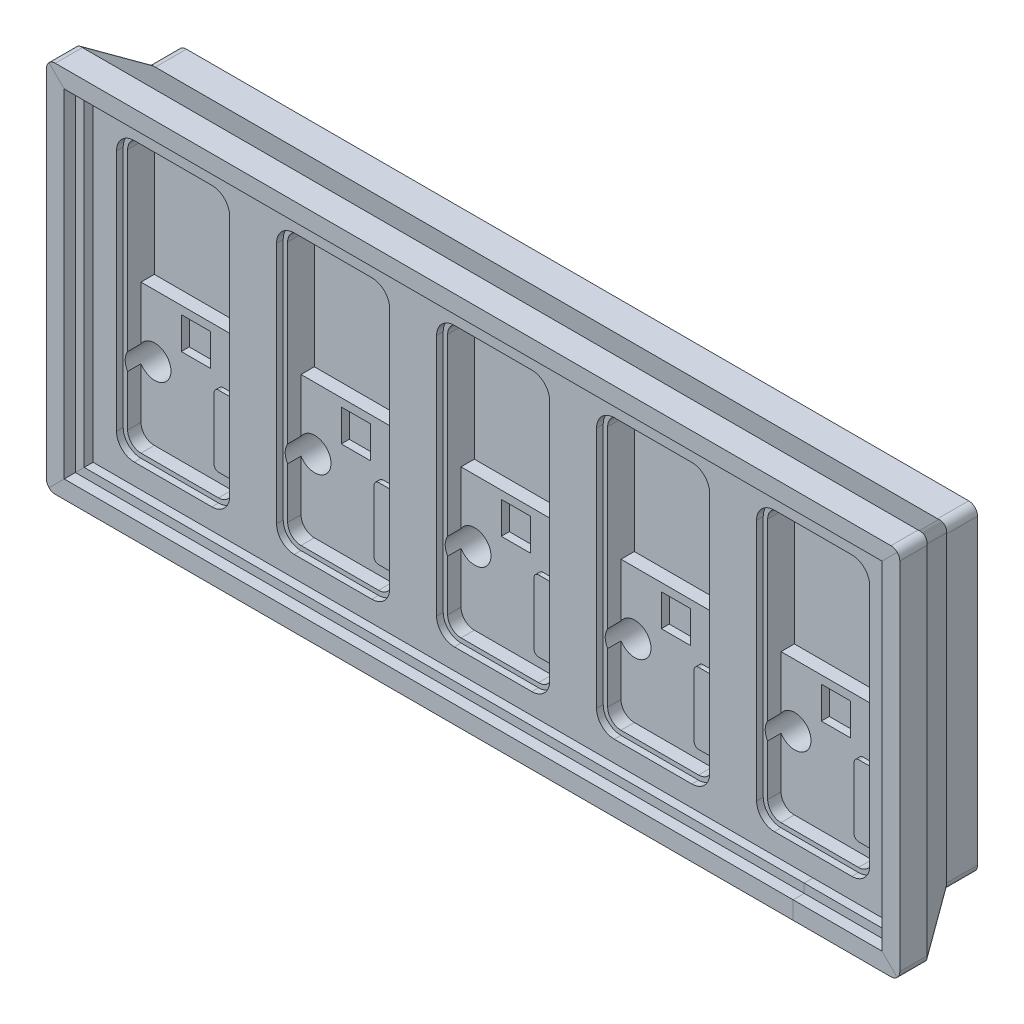
SolidWorks part; units mm, degrees
ref_plane "Ebene vorne" through (0, 0, 0) normal (0, 0, 1) x (1, 0, 0)
ref_plane "Ebene oben" through (0, 0, 0) normal (0, 1, 0) x (1, 0, 0)
ref_plane "Ebene rechts" through (0, 0, 0) normal (1, 0, 0) x (0, 0, -1)
sketch "Skizze1" plane through (0, 0, 0) normal (0, 0, 1) x (1, 0, 0)
  line L1 (-18, -36) -> (18, -36)
  line L2 (-18, -36) -> (-18, 36)
  line L3 (-18, 36) -> (18, 36)
  line L4 (18, -36) -> (18, 36)
  line L5 (-18, -36) -> (18, 36) construction
  line L6 (-18, 36) -> (18, -36) construction
  point P0 (0, 0)
  dimension "D1" = 72
  dimension "D2" = 36
extrude "Aufsatz-Linear austragen1" add sketch "Skizze1" along normal blind 19
sketch "Skizze2" plane through (0, 0, 19) normal (0, 0, 1) x (1, 0, 0)
  line L1 (-8.725, -31.325) -> (8.725, -31.325)
  line L2 (-12.725, -27.325) -> (-12.725, 27.325)
  line L3 (-8.725, 31.325) -> (8.725, 31.325)
  line L4 (12.725, -27.325) -> (12.725, 27.325)
  line L5 (-12.725, -31.325) -> (12.725, 31.325) construction
  line L6 (-12.725, 31.325) -> (12.725, -31.325) construction
  arc A0 (-12.725, -27.325) -> (-8.725, -31.325) centre (-8.725, -27.325) ccw
  arc A1 (8.725, -31.325) -> (12.725, -27.325) centre (8.725, -27.325) ccw
  arc A2 (8.725, 31.325) -> (12.725, 27.325) centre (8.725, 27.325) cw
  arc A3 (-12.725, 27.325) -> (-8.725, 31.325) centre (-8.725, 27.325) cw
  point P0 (0, 0)
  dimension "4" = 4
  dimension "D2" = 25.45
  dimension "D3" = 62.65
extrude "Schnitt-Linear austragen1" cut sketch "Skizze2" against normal blind 1.5
sketch "Skizze3" plane through (0, 0, 17.5) normal (0, 0, 1) x (1, 0, 0)
  line L8 (-8.725, -30.325) -> (8.725, -30.325)
  line L9 (11.725, -27.325) -> (11.725, 27.325)
  line L10 (8.725, 30.325) -> (-8.725, 30.325)
  line L11 (-11.725, 27.325) -> (-11.725, -27.325)
  line L12 (-8.725, -30.325) -> (8.725, -30.325)
  line L13 (11.725, -27.325) -> (11.725, 27.325)
  line L14 (8.725, 30.325) -> (-8.725, 30.325)
  line L15 (-11.725, 27.325) -> (-11.725, -27.325)
  arc A8 (-11.725, -27.325) -> (-8.725, -30.325) centre (-8.725, -27.325) ccw
  arc A9 (8.725, -30.325) -> (11.725, -27.325) centre (8.725, -27.325) ccw
  arc A10 (11.725, 27.325) -> (8.725, 30.325) centre (8.725, 27.325) ccw
  arc A11 (-8.725, 30.325) -> (-11.725, 27.325) centre (-8.725, 27.325) ccw
  arc A12 (-11.725, -27.325) -> (-8.725, -30.325) centre (-8.725, -27.325) ccw
  arc A13 (8.725, -30.325) -> (11.725, -27.325) centre (8.725, -27.325) ccw
  arc A14 (11.725, 27.325) -> (8.725, 30.325) centre (8.725, 27.325) ccw
  arc A15 (-8.725, 30.325) -> (-11.725, 27.325) centre (-8.725, 27.325) ccw
  dimension "D1" = 1
extrude "Schnitt-Linear austragen2" cut sketch "Skizze3" against normal blind 3
sketch "Skizze4" plane through (0, 0, 14.5) normal (0, 0, 1) x (1, 0, 0)
  line L0 (-11.725, 0) -> (11.725, 0)
  line L1 (-11.725, 0) -> (-11.725, 27.325)
  line L2 (11.725, 27.325) -> (11.725, 0)
  line L4 (-8.725, -30.325) -> (8.725, -30.325)
  line L5 (11.725, -27.325) -> (11.725, 27.325)
  line L6 (8.725, 30.325) -> (-8.725, 30.325)
  line L7 (-11.725, 27.325) -> (-11.725, -27.325)
  line L8 (-8.725, -30.325) -> (8.725, -30.325) construction
  line L9 (11.725, -27.325) -> (11.725, 27.325) construction
  line L10 (8.725, 30.325) -> (-8.725, 30.325)
  line L11 (-11.725, 27.325) -> (-11.725, -27.325) construction
  arc A4 (-11.725, -27.325) -> (-8.725, -30.325) centre (-8.725, -27.325) ccw
  arc A5 (8.725, -30.325) -> (11.725, -27.325) centre (8.725, -27.325) ccw
  arc A6 (11.725, 27.325) -> (8.725, 30.325) centre (8.725, 27.325) ccw
  arc A7 (-8.725, 30.325) -> (-11.725, 27.325) centre (-8.725, 27.325) ccw
  arc A8 (-11.725, -27.325) -> (-8.725, -30.325) centre (-8.725, -27.325) ccw construction
  arc A9 (8.725, -30.325) -> (11.725, -27.325) centre (8.725, -27.325) ccw construction
  arc A10 (11.725, 27.325) -> (8.725, 30.325) centre (8.725, 27.325) ccw
  arc A11 (-8.725, 30.325) -> (-11.725, 27.325) centre (-8.725, 27.325) ccw
  dimension "D1" = 0
extrude "Schnitt-Linear austragen3" cut sketch "Skizze4" against normal blind 3
sketch "Skizze5" plane through (0, 0, 17.5) normal (0, 0, 1) x (1, 0, 0)
  circle A0 centre (-8.63, -13.97) radius 3.65
  dimension "D1" = 7.3
  dimension "D2" = 13.97
  dimension "D3" = 8.63
extrude "Schnitt-Linear austragen4" cut sketch "Skizze5" against normal blind 15.5
sketch "Skizze6" plane through (0, 0, 17.5) normal (0, 0, 1) x (1, 0, 0)
  line L0 (-2.66, -1.8) -> (3.94, -9) construction
  line L1 (3.94, -1.8) -> (-2.66, -1.8)
  line L2 (3.94, -1.8) -> (3.94, -9)
  line L3 (3.94, -9) -> (-2.66, -9)
  line L4 (-2.66, -1.8) -> (-2.66, -9)
  point P6 (0.64, -5.4)
  dimension "D1" = 5.4
  dimension "D2" = 0.64
  dimension "D3" = 6.6
  dimension "D4" = 7.2
extrude "Schnitt-Linear austragen5" cut sketch "Skizze6" against normal blind 4.8 contours L2 L3 L4 L1
sketch "Skizze7" plane through (0, 0, 14.5) normal (0, 0, 1) x (1, 0, 0)
  line L1 (11.725, -27.325) -> (5.725, -27.325)
  line L2 (11.725, -27.325) -> (11.725, -11.325)
  line L3 (11.725, -11.325) -> (5.725, -11.325)
  line L4 (5.725, -27.325) -> (5.725, -11.325)
  dimension "D1" = 6
  dimension "D2" = 16
extrude "Aufsatz-Linear austragen2" add sketch "Skizze7" along normal blind 1
fillet "Verrundung2" radius 1 4 edges at (11.725, -27.325, 15) (5.725, -27.325, 15) (5.725, -11.325, 15) (11.725, -11.325, 15)
pattern_linear "Lineares Muster3" count 5 spacing 36 along (-1, 0, 0) of "Schnitt-Linear austragen1", "Schnitt-Linear austragen2", "Schnitt-Linear austragen3", "Schnitt-Linear austragen4", "Schnitt-Linear austragen5", "Aufsatz-Linear austragen2", "Verrundung2", "Aufsatz-Linear austragen1"
sketch "Skizze8" plane through (0, 0, 0) normal (1, 0, 0) x (0, 0, -1)
  line L0 (-7, -36) -> (-17.3923, -42)
  line L1 (-17.3923, -42) -> (-23.5, -42)
  line L2 (-23.5, -42) -> (-23.5, -38)
  line L3 (-23.5, -38) -> (-21, -38)
  line L4 (0, -36) -> (0, 36)
  line L5 (0, 36) -> (-19, 36)
  line L6 (-19, 36) -> (-19, -36)
  line L7 (-19, -36) -> (0, -36)
  line L8 (0, -36) -> (0, 36) construction
  line L9 (0, 36) -> (-19, 36) construction
  line L10 (-19, 36) -> (-19, -36) construction
  line L11 (-19, -36) -> (0, -36) construction
  line L13 (-19, -36) -> (-7, -36)
  line L14 (-21, -38) -> (-21, -36)
  line L15 (-21, -36) -> (-19, -36)
  dimension "D2" = 2
  dimension "D3" = 2.5
  dimension "D4" = 2
  dimension "D5" = 4
  dimension "D6" = 12
  dimension "D7" = 30
  dimension "D1" = 0
sketch "Skizze9" plane through (0, 0, 19) normal (0, 0, 1) x (1, 0, 0)
  line L0 (18, 36) -> (-162, 36) construction
  line L1 (18, 36) -> (-162, 36)
  line L2 (-162, 36) -> (-162, -36) construction
  line L3 (-162, -36) -> (18, -36) construction
  line L4 (18, -36) -> (18, 36) construction
  line L5 (-162, 36) -> (-162, -36)
  line L6 (-162, -36) -> (18, -36)
  line L7 (18, -36) -> (18, 36)
sweep "Austragung1" add profiles "Skizze8" path "Skizze9"
fillet "Verrundung3" radius 2 12 edges at (24, -42, 20.4462) (21, -39, 12.1962) (18, -36, 3.5) (24, 42, 20.4462) (21, 39, 12.1962) (18, 36, 3.5) (-168, 42, 20.4462) (-165, 39, 12.1962) (-162, 36, 3.5) (-168, -42, 20.4462) (-165, -39, 12.1962) (-162, -36, 3.5)
